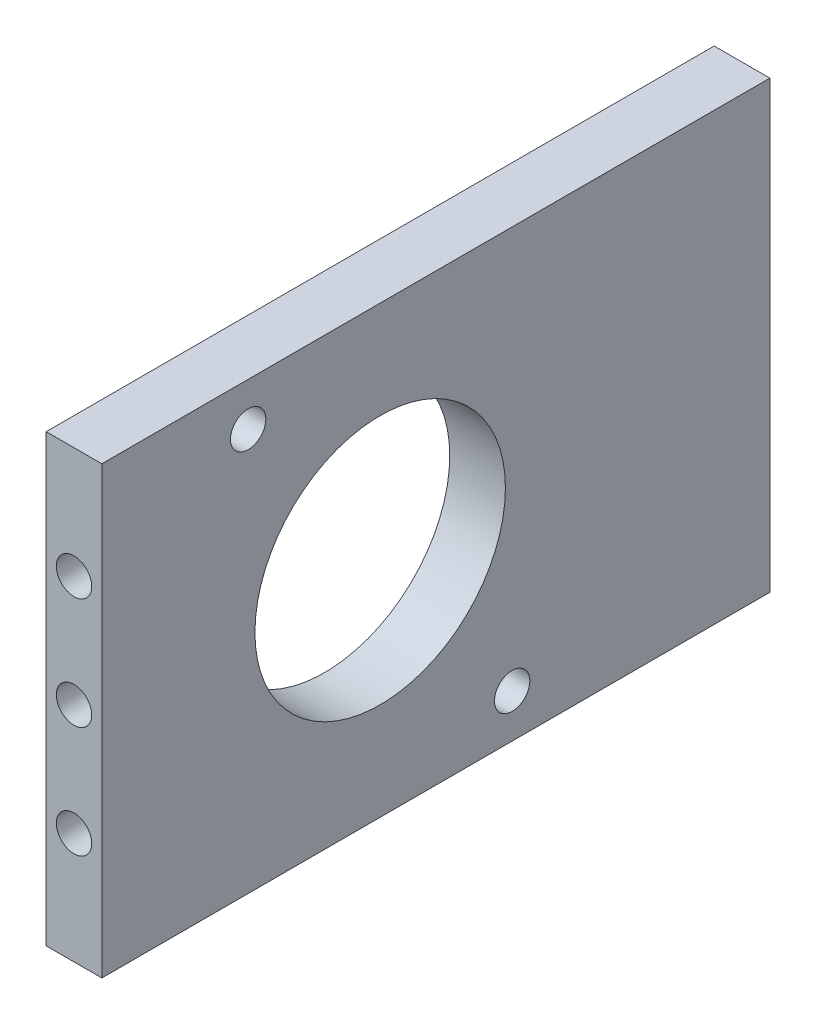
SolidWorks part; units mm, degrees
material "6061-T6 (SS)"
ref_plane "Front" through (0, 0, 0) normal (0, 0, 1) x (1, 0, 0)
ref_plane "Top" through (0, 0, 0) normal (0, 1, 0) x (1, 0, 0)
ref_plane "Right" through (0, 0, 0) normal (1, 0, 0) x (0, 0, -1)
sketch "Sketch2" plane through (0, 0, 0) normal (1, 0, 0) x (0, 0, -1)
  line L1 (-38.1, -25.4) -> (38.1, -25.4)
  line L2 (-38.1, -25.4) -> (-38.1, 25.4)
  line L3 (-38.1, 25.4) -> (38.1, 25.4)
  line L4 (38.1, -25.4) -> (38.1, 25.4)
  line L5 (-38.1, -25.4) -> (38.1, 25.4) construction
  line L6 (-38.1, 25.4) -> (38.1, -25.4) construction
  point P0 (0, 0)
  dimension "D1" = 76.2
  dimension "D2" = 50.8
extrude "Boss-Extrude2" add sketch "Sketch2" along normal blind 6.35
hole_wizard "#10-32 Tapped Hole1" positions "Sketch3" profile "Sketch5" tap size "#10-32" standard "ANSI Inch"
sketch "Sketch3" plane through (0, 0, 38.1) normal (0, 0, 1) x (1, 0, 0)
  line L0 (3.175, 25.4) -> (3.175, 12.7) construction
  line L1 (6.35, 25.4) -> (0, 25.4) construction
  line L3 (3.175, 12.7) -> (3.175, 0) construction
  line L4 (3.175, 0) -> (3.175, -12.7) construction
  line L5 (3.175, -12.7) -> (3.175, -25.4) construction
  line L6 (6.35, -25.4) -> (0, -25.4) construction
  point P0 (3.175, -12.7)
  point P2 (3.175, 0)
  point P6 (3.175, 12.7)
sketch "Sketch5" plane through (3.175, -12.7, 38.1) normal (1, 0, 0) x (0, -1, 0)
  line L0 (0, 0) -> (0, 13.2428)
  line L1 (0, 13.2428) -> (2.0193, 12.0294)
  line L2 (2.0193, 12.0294) -> (2.0193, 0)
  line L5 (2.0193, 0) -> (0, 0)
  line L10 (0, 13.2428) -> (-2.0193, 12.0294) construction
  line L11 (0, -6.35) -> (0, 107.95) construction
  dimension "Tap Drill Dia." = 4.0386
  dimension "Tap Drill Depth" = 12.0294
  dimension "Drill Angle" = 118
cosmetic thread "Hole Thread1" parameters "D1"=9.652, "D2"=4.826
cosmetic thread "Hole Thread3" parameters "D1"=9.652, "D2"=4.826
cosmetic thread "Hole Thread4" parameters "D1"=9.652, "D2"=4.826
sketch "Sketch6" plane through (6.35, 0, 0) normal (1, 0, 0) x (0, 0, -1)
  line L0 (-38.1, 25.4) -> (-38.1, -25.4) construction
  line L1 (-38.1, -25.4) -> (38.1, -25.4) construction
  circle A0 centre (-6.35, 0) radius 14.2875
  dimension "D1" = 31.75
  dimension "D3" = 28.575
  dimension "D2" = 25.4
extrude "Cut-Extrude1" cut sketch "Sketch6" against normal through all
sketch "Sketch10" plane through (0, 0, 0) normal (-1, 0, 0) x (0, 0, 1)
  point P3 (-8.7041, -20.4408)
  point P8 (21.4132, 20.4687)
hole_wizard "#10-32 Tapped Hole2" positions "Sketch10" profile "Sketch9" tap size "#10-32" standard "ANSI Inch"
sketch "Sketch9" plane through (0, -20.4408, -8.7041) normal (0, 1, 0) x (0, 0, 1)
  line L0 (0, 0) -> (0, 13.2428)
  line L1 (0, 13.2428) -> (2.0193, 12.0294)
  line L2 (2.0193, 12.0294) -> (2.0193, 0)
  line L5 (2.0193, 0) -> (0, 0)
  line L10 (0, 13.2428) -> (-2.0193, 12.0294) construction
  line L11 (0, -6.35) -> (0, 107.95) construction
  dimension "Tap Drill Dia." = 4.0386
  dimension "Tap Drill Depth" = 12.0294
  dimension "Drill Angle" = 118
cosmetic thread "Hole Thread5" parameters "D1"=9.652, "D2"=4.826
cosmetic thread "Hole Thread6" parameters "D1"=9.652, "D2"=4.826
